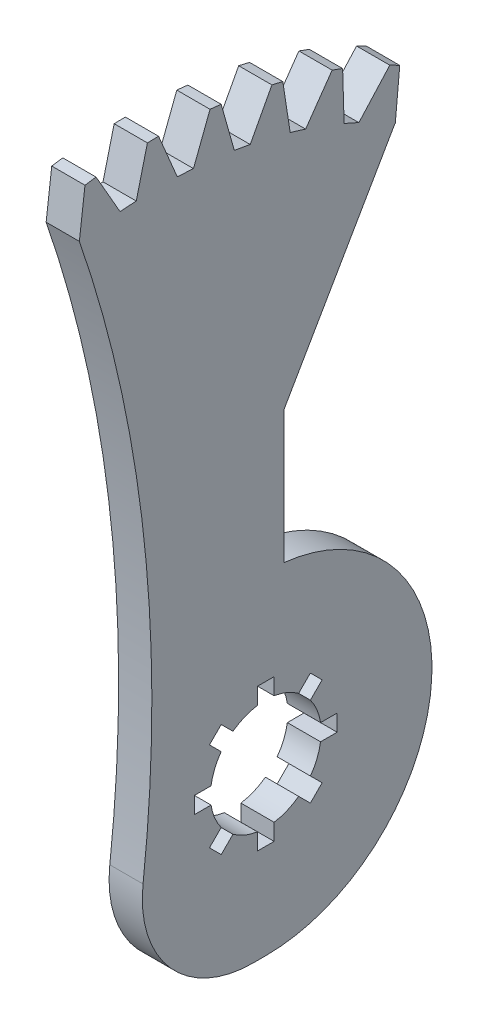
SolidWorks part; units mm, degrees
material "AISI 1045 Steel, cold drawn"
ref_plane "Front Plane" through (0, 0, 0) normal (1, 0, 0) x (0, 1, 0)
ref_plane "Top Plane" through (0, 0, 0) normal (0, 0, 1) x (0, 1, 0)
ref_plane "Right Plane" through (0, 0, 0) normal (0, 1, 0) x (-1, 0, 0)
sketch "Sketch1" plane through (0, 0, 0) normal (1, 0, 0) x (0, 1, 0)
  line L0 (-21.1875, 0) -> (76.7115, 0) construction
  line L1 (14.9079, -1.66) -> (26.9079, -1.66)
  line L2 (26.9079, -1.66) -> (44.2284, -11.66)
  line L4 (49.2594, 16.83) -> (53.3944, 16.3223)
  line L5 (46.9383, 16.83) -> (56.4733, 16.83) construction
  line L6 (53.5326, 15.3223) -> (49.7427, 13.1518)
  line L7 (-16.6602, 12.9) -> (17.3425, 12.9) construction
  line L9 (48.7493, 13.1518) -> (51.8112, 13.1518) construction
  line L11 (14.9079, -5.66) -> (25.8361, -5.66) construction
  line L12 (25.8361, -5.66) -> (45.5407, -17.0365) construction
  line L14 (0, 8.355) -> (0, -9.559) construction
  line L15 (-15, 0) -> (-15, 12.9)
  line L16 (-0.75, 6.44) -> (0.75, 6.44)
  line L17 (-0.75, 6.44) -> (-0.75, 4.9434)
  line L19 (0.75, 6.44) -> (0.75, 4.9434)
  line L20 (-15, 12.9) -> (-7.6544, 12.9) construction
  line L21 (15, 10.3875) -> (15, 0) construction
  line L22 (7.6544, 12.9) -> (15, 12.9) construction
  line L23 (-7.6544, 12.9) -> (7.6544, 12.9) construction
  line L24 (15, 12.9) -> (15, 10.3875) construction
  arc A0 (-15, 0) -> (15, 0) centre (0, 0) ccw
  circle A1 centre (0, 0) radius 5
  arc A2 (-15, 12.9) -> (49.2594, 16.83) centre (10.0139, 131.2147) ccw
  arc A4 (35.0996, 41.6143) -> (44.2284, -11.66) centre (7.6417, 9.49) cw
  arc A5 (53.3944, 16.3223) -> (53.5326, 15.3223) centre (7.6417, 9.49) cw
  arc A6 (7.6544, 12.9) -> (-7.6544, 12.9) centre (0, 0) ccw construction
  arc A7 (35.0996, 41.6143) -> (44.2284, -11.66) centre (7.6417, 9.49) cw construction
  arc A8 (37.6985, 44.655) -> (45.5407, -17.0365) centre (7.6417, 9.49) cw construction
  arc A9 (-7.6544, 12.9) -> (-9.2282, 11.8254) centre (0, 0) ccw construction
  arc A10 (10.9158, 10.2881) -> (7.6544, 12.9) centre (0, 0) ccw construction
  arc A11 (15, 0) -> (10.9158, 10.2881) centre (0, 0) ccw construction
  arc A12 (-9.2282, 11.8254) -> (-15, 0) centre (0, 0) ccw construction
  point P40 (0, 6.44)
  dimension "D1" = 10
  dimension "D2" = 30
  dimension "D3" = 120.93
  dimension "D8" = 12.9
  dimension "D9" = 4
  dimension "D10" = 42.26
  dimension "D4" = 12
  dimension "D5" = 20
  dimension "D6" = 16.83
  dimension "D7" = 323.2
  dimension "D11" = 150
  dimension "D12" = 3.41
  dimension "D13" = 7
  dimension "D14" = 1
  dimension "D15" = 14.56
  dimension "D19" = 1.5
  dimension "D20" = 6.44
extrude "Boss-Extrude1" add sketch "Sketch1" along normal blind 3 contours A4 A2 L15 A0 L1 L2 A1 L17 L16 L19 | A1 L19 L16 L17 region at (0, 17.2826, 1.5451) region at (0, 0, 5.7105)
extrude "Cut-Extrude1" cut sketch "Sketch1<3>" along normal through all both and the other way through all contours A1 L19 L16 L17 region at (0, 0, 5.7105)
sketch "Sketch1<3>" plane through (0, 0, 0) normal (1, 0, 0) x (0, 1, 0) same geometry as "Sketch1"
pattern_circular "CirPattern1" count 8 over 360 about axis through (3, 0, 0) along (1, 0, 0) of "Cut-Extrude1"
extrude "Boss-Extrude2" add sketch "Sketch1<4>" along normal blind 3 contours A5 L4 A4 L6 region at (0, 51.122, 15.3305)
sketch "Sketch1<4>" plane through (0, 0, 0) normal (1, 0, 0) x (0, 1, 0) same geometry as "Sketch1"
pattern_circular "CirPattern2" count 6 over 35.051 about axis through (3, 7.6417, 9.49) along (-1, 0, 0) of "Boss-Extrude2"
pattern_curve "CrvPattern2" [suppressed] of bodies 104 parameters "D1"=6, "D3"=50, "D2"=1, "D4"=50
ref_axis "Axis1" through (-0.15, 0, 0) along (1, 0, 0)
fillet "Fillet1" radius 10 1 edges at (1.5, -15, 12.9)
